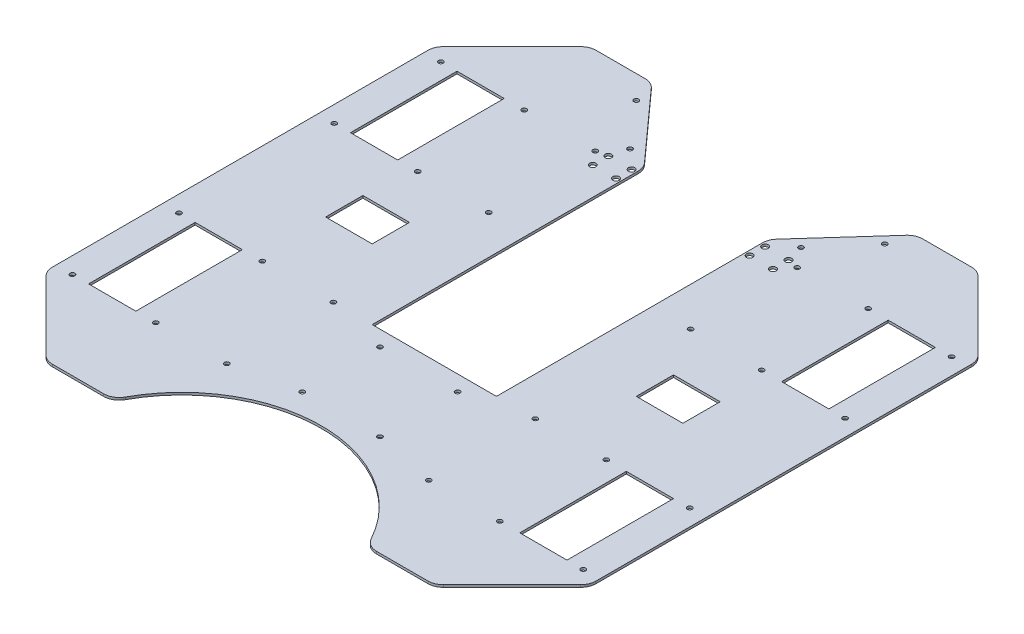
SolidWorks part; units mm, degrees
material "PMMA"
ref_plane "前视基准面" through (0, 0, 0) normal (0, 0, 1) x (1, 0, 0)
ref_plane "上视基准面" through (0, 0, 0) normal (0, 1, 0) x (1, 0, 0)
ref_plane "右视基准面" through (0, 0, 0) normal (1, 0, 0) x (0, 0, -1)
other "Configuration Table"
sketch "草图1" plane through (0, 0, 0) normal (0, 1, 0) x (1, 0, 0)
  line L0 (-125, 175) -> (-175, 125)
  line L1 (125, -175) -> (81.7103, -175)
  line L2 (175, -125) -> (175, 125)
  line L3 (125, 175) -> (85, 175)
  line L4 (-175, -125) -> (-175, 125)
  line L5 (-85, 175) -> (-40, 125)
  line L7 (125, 175) -> (175, 125)
  line L8 (175, -125) -> (125, -175)
  line L9 (-125, -175) -> (-175, -125)
  line L10 (40, 125) -> (85, 175)
  line L11 (-85, 175) -> (-125, 175)
  line L12 (40, 125) -> (40, 85)
  line L13 (40, 85) -> (-40, 85)
  line L14 (-40, 85) -> (-40, 125)
  line L15 (-153.994, 50) -> (-123.594, 50)
  line L16 (-123.594, 50) -> (-123.594, 118.58)
  line L17 (-123.594, 118.58) -> (-153.994, 118.58)
  line L18 (-153.994, 118.58) -> (-153.994, 50)
  line L19 (123.594, 50) -> (153.994, 50)
  line L20 (153.994, 50) -> (153.994, 118.58)
  line L21 (153.994, 118.58) -> (123.594, 118.58)
  line L22 (123.594, 118.58) -> (123.594, 50)
  line L23 (-175, 0) -> (175, 0) construction
  line L24 (-123.594, -118.58) -> (-153.994, -118.58)
  line L25 (-123.594, -50) -> (-123.594, -118.58)
  line L26 (-153.994, -50) -> (-123.594, -50)
  line L27 (-153.994, -118.58) -> (-153.994, -50)
  line L28 (153.994, -118.58) -> (123.594, -118.58)
  line L29 (153.994, -50) -> (153.994, -118.58)
  line L30 (123.594, -50) -> (153.994, -50)
  line L31 (123.594, -118.58) -> (123.594, -50)
  line L32 (-81.7103, -175) -> (-125, -175)
  line L33 (-80, 160) -> (-55, 131) construction
  line L34 (0, 85) -> (0, -124.4881) construction
  line L35 (-40, 85) -> (-40, -25)
  line L36 (-40, -25) -> (40, -25)
  line L37 (40, -25) -> (40, 85)
  circle A0 centre (-55, 131) radius 1.55
  circle A1 centre (-80, 160) radius 1.55
  circle A2 centre (55, 131) radius 1.55
  circle A3 centre (80, 160) radius 1.55
  circle A4 centre (-65, 118.58) radius 1.55
  circle A5 centre (-65, 50) radius 1.55
  circle A6 centre (-110.72, 50) radius 1.55
  circle A7 centre (-110.72, 118.58) radius 1.55
  circle A12 centre (-164.434, 118.58) radius 1.55
  circle A13 centre (-164.434, 50) radius 1.55
  circle A14 centre (-65, -118.58) radius 1.55
  circle A15 centre (-65, -50) radius 1.55
  circle A16 centre (-110.72, -50) radius 1.55
  circle A17 centre (-110.72, -118.58) radius 1.55
  circle A18 centre (-164.434, -50) radius 1.55
  circle A19 centre (-164.434, -118.58) radius 1.55
  circle A20 centre (65, 50) radius 1.55
  circle A21 centre (110.72, 50) radius 1.55
  circle A22 centre (110.72, 118.58) radius 1.55
  circle A23 centre (65, 118.58) radius 1.55
  circle A24 centre (164.434, 118.58) radius 1.55
  circle A25 centre (164.434, 50) radius 1.55
  circle A26 centre (164.434, -118.58) radius 1.55
  circle A27 centre (164.434, -50) radius 1.55
  circle A28 centre (110.72, -50) radius 1.55
  circle A29 centre (110.72, -118.58) radius 1.55
  circle A30 centre (65, -118.58) radius 1.55
  circle A31 centre (65, -50) radius 1.55
  arc A32 (-81.7103, -175) -> (81.7103, -175) centre (0, -212.7283) cw
  circle A33 centre (25, -60) radius 1.55
  circle A34 centre (25, -110) radius 1.55
  circle A35 centre (-25, -60) radius 1.55
  circle A36 centre (-25, -110) radius 1.55
  circle A37 centre (-43, 120) radius 2.05
  circle A38 centre (-43, 110) radius 2.05
  circle A39 centre (-58, 110) radius 2.05
  circle A40 centre (-58, 120) radius 2.05
  circle A41 centre (43, 120) radius 2.05
  circle A42 centre (58, 120) radius 2.05
  circle A43 centre (58, 110) radius 2.05
  circle A44 centre (43, 110) radius 2.05
  point P0 (0, 0)
  point P1 (-85, 175)
  point P2 (85, 175)
  point P3 (40, 125)
  point P4 (-40, 125)
  point P6 (125, 175)
  point P8 (175, 125)
  point P10 (175, -125)
  point P11 (125, -175)
  point P12 (-125, -175)
  point P13 (-175, -125)
  point P24 (-80, 160)
  point P25 (-55, 131)
  point P26 (55, 131)
  point P27 (80, 160)
  point P36 (-164.434, 118.58)
  point P37 (-164.434, 50)
  point P38 (-153.994, 118.58)
  point P39 (-123.594, 50)
  point P40 (-110.72, 118.58)
  point P41 (-110.72, 50)
  point P42 (-65, 118.58)
  point P43 (-65, 50)
  point P47 (-123.594, 118.58)
  point P53 (-153.994, 50)
  point P66 (-40, 85)
  point P67 (40, 85)
  point P70 (110.72, 50)
  point P71 (65, 50)
  point P72 (123.594, 50)
  point P73 (153.994, 50)
  point P74 (164.434, 50)
  point P75 (65, 118.58)
  point P76 (110.72, 118.58)
  point P77 (123.594, 118.58)
  point P78 (153.994, 118.58)
  point P81 (164.434, 118.58)
  point P85 (-65, -118.58)
  point P88 (-65, -50)
  point P91 (-110.72, -50)
  point P94 (-110.72, -118.58)
  point P101 (-164.434, -50)
  point P104 (-164.434, -118.58)
  point P118 (164.434, -118.58)
  point P121 (164.434, -50)
  point P128 (110.72, -50)
  point P131 (110.72, -118.58)
  point P134 (65, -118.58)
  point P137 (65, -50)
  point P157 (58, 110)
  point P158 (43, 110)
  point P159 (43, 120)
  point P160 (58, 120)
  point P171 (0, 0)
  dimension "D29" = 3.1
  dimension "D30" = 3.1
  dimension "D31" = 3.1
  dimension "D32" = 3.1
  dimension "D40" = 3.1
  dimension "D41" = 3.1
  dimension "D42" = 3.1
  dimension "D43" = 3.1
  dimension "D44" = 3.1
  dimension "D45" = 3.1
  dimension "D46" = 3.1
  dimension "D47" = 3.1
  dimension "D48" = 3.1
  dimension "D49" = 3.1
  dimension "D60" = 3.1
  dimension "D61" = 3.1
  dimension "D62" = 43.2897
  dimension "D63" = 90
  dimension "D67" = 3.1
  dimension "D68" = 3.1
  dimension "D69" = 3.1
  dimension "D70" = 3.1
  dimension "D75" = 4.1
  dimension "D76" = 4.1
  dimension "D77" = 4.1
  dimension "D78" = 4.1
  dimension "D80" = 110
  dimension "D1" = 175
  dimension "D2" = 175
  dimension "D3" = 125
  dimension "D4" = 125
  dimension "D5" = 125
  dimension "D6" = 125
  dimension "D7" = 125
  dimension "D8" = 125
  dimension "D9" = 125
  dimension "D10" = 125
  dimension "D11" = 175
  dimension "D12" = 175
  dimension "D13" = 40
  dimension "D14" = 40
  dimension "D15" = 85
  dimension "D16" = 85
  dimension "D17" = 125
  dimension "D18" = 125
  dimension "D19" = 40
  dimension "D20" = 45
  dimension "D21" = 160
  dimension "D22" = 160
  dimension "D23" = 80
  dimension "D24" = 80
  dimension "D25" = 55
  dimension "D26" = 131
  dimension "D27" = 55
  dimension "D28" = 131
  dimension "D33" = 50
  dimension "D34" = 118.58
  dimension "D35" = 65
  dimension "D36" = 45.72
  dimension "D37" = 12.874
  dimension "D38" = 30.4
  dimension "D39" = 10.44
  dimension "D50" = 40
  dimension "D51" = 40
  dimension "D52" = 85
  dimension "D53" = 85
  dimension "D54" = 138.013
  dimension "D55" = 65
  dimension "D56" = 45.72
  dimension "D57" = 12.874
  dimension "D58" = 30.4
  dimension "D59" = 10.44
  dimension "D64" = 0
  dimension "D65" = 25
  dimension "D66" = 25
  dimension "D71" = 60
  dimension "D72" = 50
  dimension "D73" = 15
  dimension "D74" = 10
  dimension "D79" = 43
  dimension "D81" = 120
  dimension "D82" = 110
extrude "凸台-拉伸1" add sketch "草图1" along normal blind 1.5 contours A1 | A0 | L8 L1 A32 L32 L9 L4 L0 L11 L5 L14 L13 L12 L10 L3 L7 L2 | A5 | A3 | A2 | A4 | A7 | A12 | L16 L17 L18 L15 | A6 | L21 L22 L19 L20 | A13 | A16 | A17 | A14 | A15 | A18 | A19 | L25 L24 L27 L26 | A20 | A21 | A22 | A23 | A24 | A25 | A28 | A26 | A27 | L28 L31 L30 L29 | A30 | A31 | A29 | A35 | A36 | A33 | A34 | A39 | A40 | A37 | A38 | A43 | A42 | A41 | A44
fillet "圆角1" radius 10 1 edges at (-40, 0.75, -125)
fillet "圆角2" radius 10 1 edges at (40, 0.75, -125)
fillet "圆角3" radius 10 12 edges at (-85, 0.75, -175) (85, 0.75, -175) (125, 0.75, -175) (175, 0.75, -125) (175, 0.75, 125) (125, 0.75, 175) (81.7103, 0.75, 175) (-81.7103, 0.75, 175) (-125, 0.75, 175) (-175, 0.75, 125) (-175, 0.75, -125) (-125, 0.75, -175)
sketch "草图2" plane through (0, 1.5, 0) normal (0, 1, 0) x (1, 0, 0)
  line L1 (-40, 85) -> (40, 85)
  line L2 (-40, 85) -> (-40, -50)
  line L3 (-40, -50) -> (40, -50)
  line L4 (40, 85) -> (40, -50)
  dimension "D1" = 80
  dimension "D2" = 135
extrude "切除-拉伸1" cut sketch "草图2" against normal blind 10
sketch "草图3" plane through (0, 1.5, 0) normal (0, 1, 0) x (1, 0, 0)
  line L0 (-87.875, -175) -> (-120.8579, -175) construction
  line L1 (-115, 19) -> (-85, 19)
  line L2 (-115, 19) -> (-115, -5)
  line L3 (-115, -5) -> (-85, -5)
  line L4 (-85, 19) -> (-85, -5)
  line L5 (-175, -120.8579) -> (-175, 120.8579) construction
  line L6 (120.8579, -175) -> (87.875, -175) construction
  line L7 (85, 19) -> (115, 19)
  line L8 (85, 19) -> (85, -5)
  line L9 (85, -5) -> (115, -5)
  line L10 (115, 19) -> (115, -5)
  line L11 (175, -120.8579) -> (175, 120.8579) construction
  dimension "D1" = 30
  dimension "D2" = 24
  dimension "D3" = 170
  dimension "D4" = 60
  dimension "D5" = 30
  dimension "D6" = 24
  dimension "D7" = 170
  dimension "D8" = 60
extrude "切除-拉伸2" cut sketch "草图3" against normal blind 10
